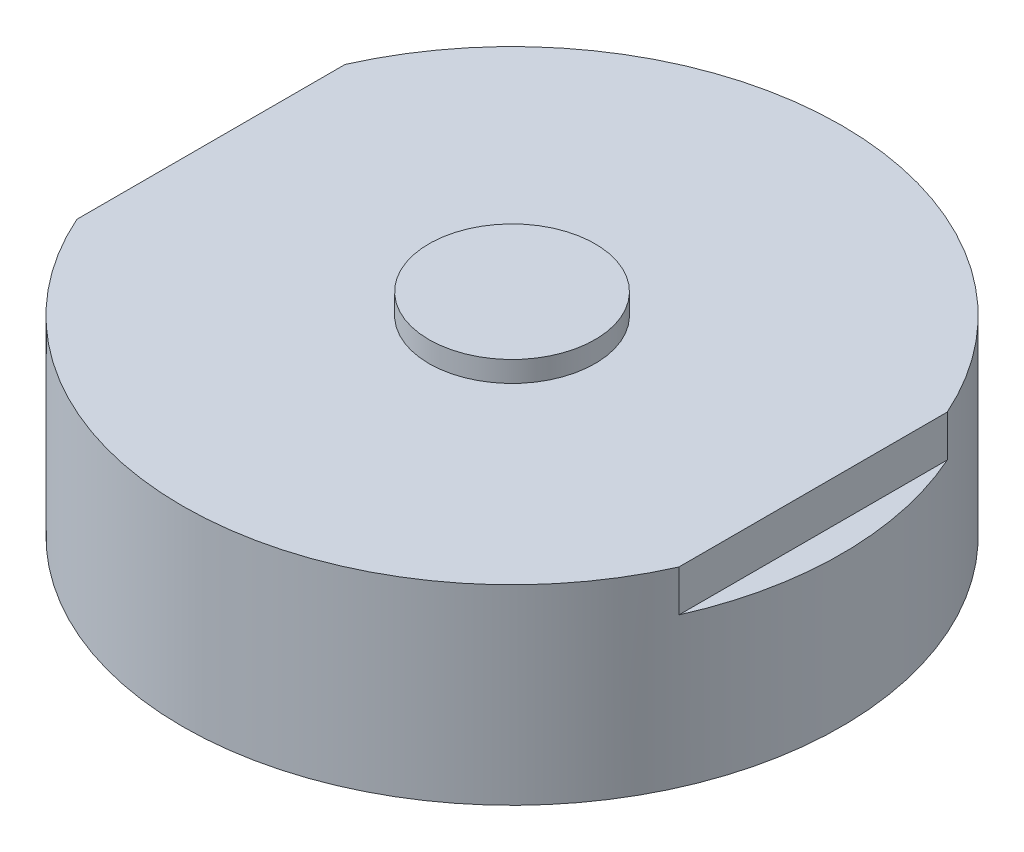
SolidWorks part; units mm, degrees
other "DetailItem1"
ref_plane "Front Plane" through (0, 0, 0) normal (0, 0, 1) x (1, 0, 0)
ref_plane "Top Plane" through (0, 0, 0) normal (0, 1, 0) x (1, 0, 0)
ref_plane "Right Plane" through (0, 0, 0) normal (1, 0, 0) x (0, 0, -1)
sketch "Sketch1" plane through (0, 0, 0) normal (0, 1, 0) x (1, 0, 0)
  circle A0 centre (0, 0) radius 15.875
  dimension "D1" = 31.75
extrude "Boss-Extrude1" add sketch "Sketch1" along normal blind 9.2
sketch "Sketch2" plane through (0, 9.2, 0) normal (0, 1, 0) x (1, 0, 0)
  line L1 (-16.7594, 7.2988) -> (-14.5, 7.2988)
  line L2 (-16.7594, 7.2988) -> (-16.7594, -8.9942)
  line L3 (-16.7594, -8.9942) -> (-14.5, -8.9942)
  line L4 (-14.5, 7.2988) -> (-14.5, -8.9942)
  line L5 (16.9539, 7.2988) -> (14.5, 7.2988)
  line L6 (16.9539, 7.2988) -> (16.9539, -11.3131)
  line L7 (16.9539, -11.3131) -> (14.5, -11.3131)
  line L8 (14.5, 7.2988) -> (14.5, -11.3131)
  dimension "D1" = 29
  dimension "D2" = 14.5
extrude "Cut-Extrude2" cut sketch "Sketch2" against normal blind 2
sketch "Sketch3" plane through (0, 9.2, 0) normal (0, 1, 0) x (1, 0, 0)
  circle A0 centre (0, 0) radius 4
  dimension "D1" = 8
extrude "Boss-Extrude3" add sketch "Sketch3" along normal blind 1
sketch "Sketch4" plane through (0, 0, 0) normal (0, -1, 0) x (1, 0, 0)
  line L0 (0, 15.875) -> (0, -15.875) construction
  line L1 (15.875, 0) -> (-15.875, 0) construction
  circle A0 centre (0, 0) radius 15.875 construction
  circle A1 centre (0, -12.7) radius 1.1095
  circle A2 centre (0, 12.7) radius 1.1095
  dimension "D1" = 25.4
extrude "Cut-Extrude3" cut sketch "Sketch4" against normal blind 1
